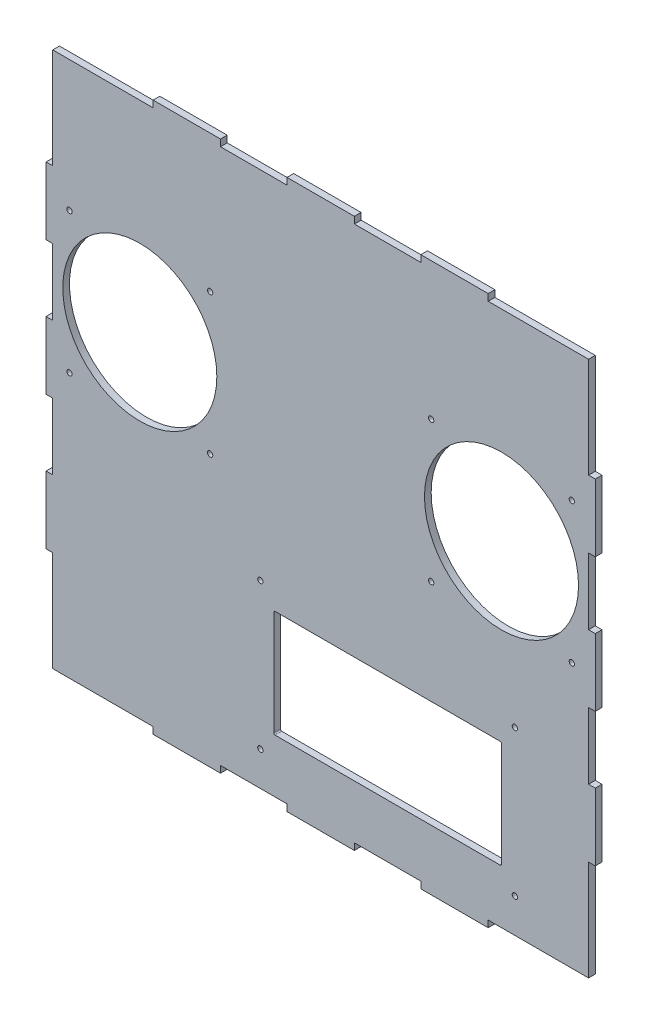
SolidWorks part; units mm, degrees
ref_plane "Ebene vorne" through (0, 0, 0) normal (0, 0, 1) x (1, 0, 0)
ref_plane "Ebene oben" through (0, 0, 0) normal (0, 1, 0) x (1, 0, 0)
ref_plane "Ebene rechts" through (0, 0, 0) normal (1, 0, 0) x (0, 0, -1)
sketch "Skizze1" plane through (0, 0, 0) normal (0, 0, 1) x (1, 0, 0)
  line L1 (0, 0) -> (410, 0)
  line L2 (0, 0) -> (0, 410)
  line L3 (0, 410) -> (410, 410)
  line L4 (410, 0) -> (410, 410)
  dimension "D1" = 410
  dimension "D2" = 410
extrude "Aufsatz-Linear austragen1" add sketch "Skizze1" along normal blind 5 contours L2 L3 L4 L1
sketch "Skizze2" plane through (0, 0, 5) normal (0, 0, 1) x (1, 0, 0)
  line L0 (0, 410) -> (410, 410) construction
  line L1 (-92.7967, 379.65) -> (5, 379.65)
  line L2 (-92.7967, 379.65) -> (-92.7967, 330.05)
  line L3 (-92.7967, 330.05) -> (5, 330.05)
  line L4 (5, 379.65) -> (5, 330.05)
  dimension "D1" = 49.6
  dimension "D2" = 5
  dimension "D3" = 79.95
extrude "Schnitt-Linear austragen1" cut sketch "Skizze2" against normal blind 5
pattern_linear "Lineares Muster1" count 4 spacing 99.9 along (0, -1, 0) of "Schnitt-Linear austragen1"
ref_plane "Ebene1" through (205, 0, 0) normal (1, 0, 0) x (0, 0, -1)
mirror "Spiegeln1" about plane through (205, 0, 0) normal (1, 0, 0) of "Schnitt-Linear austragen1", "Lineares Muster1"
sketch "Skizze3" plane through (0, 0, 5) normal (0, 0, 1) x (1, 0, 0)
  line L0 (0, 410) -> (410, 410) construction
  line L1 (30.35, 446.7791) -> (79.95, 446.7791)
  line L2 (30.35, 446.7791) -> (30.35, 405)
  line L3 (30.35, 405) -> (79.95, 405)
  line L4 (79.95, 446.7791) -> (79.95, 405)
  dimension "D1" = 49.6
  dimension "D2" = 5
  dimension "D3" = 79.95
extrude "Schnitt-Linear austragen2" cut sketch "Skizze3" against normal blind 5
pattern_linear "Lineares Muster2" count 4 spacing 99.9 along (1, 0, 0) of "Schnitt-Linear austragen2"
ref_plane "Ebene2" through (0, 205, 0) normal (0, 1, 0) x (1, 0, 0)
mirror "Spiegeln2" about plane through (0, 205, 0) normal (0, 1, 0) of "Schnitt-Linear austragen2", "Lineares Muster2"
sketch "Skizze4" plane through (0, 0, 5) normal (0, 0, 1) x (1, 0, 0)
  line L0 (5, 379.65) -> (5, 405)
  line L1 (30.35, 405) -> (5, 405)
  line L7 (5, 379.65) -> (-47.8629, 379.65)
  line L10 (-47.8629, 379.65) -> (-47.8629, 405)
  line L12 (-47.8629, 405) -> (-47.8629, 431.5498)
  line L13 (-47.8629, 431.5498) -> (5, 431.5498)
  line L17 (5, 431.5498) -> (30.35, 431.5498)
  line L18 (30.35, 405) -> (30.35, 431.5498)
extrude "Schnitt-Linear austragen3" cut sketch "Skizze4" against normal blind 5
mirror "Spiegeln3" about plane through (205, 0, 0) normal (1, 0, 0) of "Schnitt-Linear austragen3"
mirror "Spiegeln4" about plane through (0, 205, 0) normal (0, 1, 0) of "Schnitt-Linear austragen3", "Spiegeln3"
sketch "Skizze5" plane through (0, 0, 0) normal (0, 0, -1) x (-1, 0, 0)
  line L0 (-255, 139.5) -> (-255, 30.5) construction
  line L1 (-5, 130.25) -> (-5, 179.85) construction
  line L2 (-339, 125) -> (-171, 125)
  line L3 (-340, 124) -> (-340, 46)
  line L4 (-339, 45) -> (-171, 45)
  line L5 (-170, 124) -> (-170, 46)
  line L6 (-155, 165) -> (-5, 165) construction
  line L7 (-155, 165) -> (-155, 5) construction
  line L8 (-155, 5) -> (-5, 5) construction
  line L9 (-5, 165) -> (-5, 5) construction
  line L10 (-130.25, 5) -> (-179.85, 5) construction
  line L11 (-5, 165) -> (-405, 165) construction
  line L12 (-355, 25.5) -> (-155, 25.5) construction
  line L13 (-405, 130.25) -> (-405, 179.85) construction
  line L14 (-405, 170) -> (-5, 170) construction
  line L15 (-355, 25.5) -> (-355, 144.5) construction
  line L16 (-392.5, 307.5) -> (-287.5, 307.5) construction
  line L17 (-392.5, 307.5) -> (-392.5, 202.5) construction
  line L18 (-392.5, 202.5) -> (-287.5, 202.5) construction
  line L19 (-287.5, 307.5) -> (-287.5, 202.5) construction
  line L20 (-355, 144.5) -> (-155, 144.5) construction
  line L21 (-155, 25.5) -> (-155, 144.5) construction
  line L22 (-350, 139.5) -> (-160, 139.5) construction
  line L23 (-350, 139.5) -> (-350, 30.5) construction
  line L24 (-350, 30.5) -> (-160, 30.5) construction
  line L25 (-160, 139.5) -> (-160, 30.5) construction
  line L26 (-350, 85) -> (-160, 85) construction
  line L28 (-400, 315) -> (-280, 195) construction
  line L29 (-400, 315) -> (-280, 315)
  line L30 (-400, 315) -> (-400, 195)
  line L31 (-400, 195) -> (-280, 195)
  line L33 (-280, 315) -> (-280, 195)
  line L34 (-400, 195) -> (-280, 315) construction
  line L37 (-230.15, 5) -> (-279.75, 5) construction
  circle A0 centre (-340, 255) radius 57.5
  circle A1 centre (-340, 255) radius 74.2462 construction
  circle A2 centre (-287.5, 307.5) radius 2
  circle A3 centre (-392.5, 202.5) radius 2
  circle A4 centre (-392.5, 307.5) radius 2
  circle A5 centre (-287.5, 202.5) radius 2
  circle A6 centre (-350, 139.5) radius 2
  circle A7 centre (-160, 139.5) radius 2
  circle A8 centre (-160, 30.5) radius 2
  circle A9 centre (-350, 30.5) radius 2
  arc A10 (-339, 45) -> (-340, 46) centre (-339, 46) cw
  arc A11 (-340, 124) -> (-339, 125) centre (-339, 124) cw
  arc A12 (-170, 124) -> (-171, 125) centre (-171, 124) ccw
  arc A13 (-170, 46) -> (-171, 45) centre (-171, 46) cw
  point P54 (-340, 45)
  point P57 (-340, 125)
  point P60 (-170, 125)
  dimension "D1" = 115
  dimension "D13" = 148.4924
  dimension "D14" = 4
  dimension "D23" = 4
  dimension "D26" = 1
  dimension "D2" = 150
  dimension "D3" = 65
  dimension "D4" = 80
  dimension "D5" = 170
  dimension "D6" = 150
  dimension "D7" = 160
  dimension "D8" = 15
  dimension "D9" = 80
  dimension "D10" = 5
  dimension "D11" = 105
  dimension "D12" = 105
  dimension "D15" = 119
  dimension "D16" = 200
  dimension "D17" = 5
  dimension "D18" = 5
  dimension "D19" = 5
  dimension "D20" = 5
  dimension "D21" = 85
  dimension "D22" = 40
  dimension "D24" = 120
  dimension "D25" = 120
extrude "Schnitt-Linear austragen4" cut sketch "Skizze5" against normal up to next contours A0 | A5 | A3 | A2 | A4
extrude "Schnitt-Linear austragen5" cut sketch "Skizze5<3>" against normal blind 10 contours L2 A12 L5 A13 L4 A10 L3 A11 | A7 | A8 | A9 | A6
sketch "Skizze5<3>" plane through (0, 0, 0) normal (0, 0, -1) x (-1, 0, 0) same geometry as "Skizze5"
mirror "Spiegeln5" about plane through (205, 0, 0) normal (1, 0, 0) of "Schnitt-Linear austragen4"
sketch "Skizze6" [suppressed] plane through (0, 0, 0) normal (0, 0, -1) x (-1, 0, 0)
  line L1 (-279.75, 395.0139) -> (-119.75, 395.0139)
  line L2 (-279.75, 395.0139) -> (-279.75, 165.0139)
  line L3 (-279.75, 165.0139) -> (-119.75, 165.0139)
  line L4 (-119.75, 395.0139) -> (-119.75, 165.0139)
  dimension "D1" = 160
  dimension "D2" = 230
